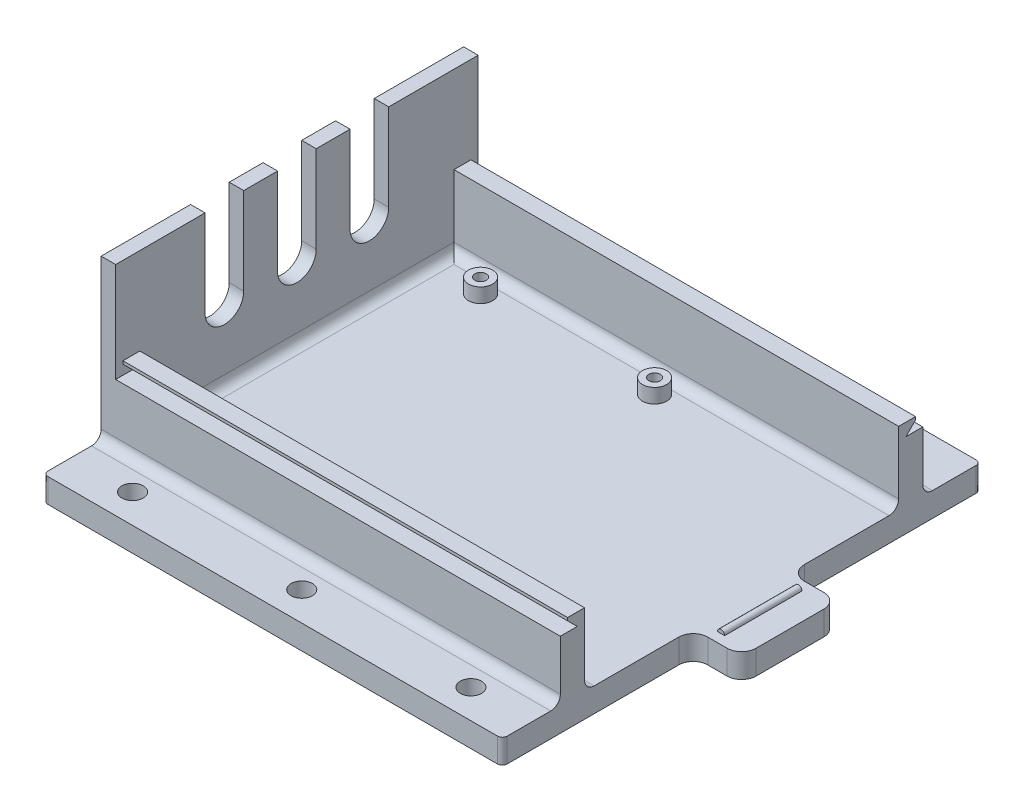
SolidWorks part; units mm, degrees
ref_plane "Front Plane" through (0, 0, 0) normal (0, 0, 1) x (1, 0, 0)
ref_plane "Top Plane" through (0, 0, 0) normal (0, 1, 0) x (1, 0, 0)
ref_plane "Right Plane" through (0, 0, 0) normal (1, 0, 0) x (0, 0, -1)
sketch "Sketch1" plane through (0, 0, 0) normal (0, 1, 0) x (1, 0, 0)
  line L0 (47.5, 13) -> (47.5, 49.5)
  line L1 (-47.5, -49.5) -> (47.5, -49.5)
  line L2 (-47.5, -49.5) -> (-47.5, 49.5)
  line L3 (-47.5, 49.5) -> (47.5, 49.5)
  line L4 (47.5, -49.5) -> (47.5, -13)
  line L5 (-47.5, -49.5) -> (47.5, 49.5) construction
  line L6 (-47.5, 49.5) -> (47.5, -49.5) construction
  line L7 (50.5, 10) -> (54.5, 10)
  line L9 (50.5, -10) -> (54.5, -10)
  line L10 (57.5, 7) -> (57.5, -7)
  arc A0 (54.5, 10) -> (57.5, 7) centre (54.5, 7) cw
  arc A1 (54.5, -10) -> (57.5, -7) centre (54.5, -7) ccw
  arc A2 (47.5, -13) -> (50.5, -10) centre (50.5, -13) cw
  arc A3 (50.5, 10) -> (47.5, 13) centre (50.5, 13) cw
  point P0 (0, 0)
  point P10 (57.5, 0)
  point P13 (57.5, 10)
  point P16 (57.5, -10)
  point P21 (47.5, 10)
  dimension "D5" = 3
  dimension "D1" = 95
  dimension "D2" = 99
  dimension "D3" = 20
  dimension "D4" = 10
extrude "Boss-Extrude1" add sketch "Sketch1" along normal blind 5
sketch "Sketch2" plane through (0, 5, 0) normal (0, 1, 0) x (1, 0, 0)
  line L0 (-47.5, 49.5) -> (-47.5, -49.5) construction
  line L1 (-47.5, 37.5) -> (47.5, 37.5)
  line L3 (-47.5, 32.5) -> (47.5, 32.5)
  line L4 (47.5, 37.5) -> (47.5, 32.5)
  line L5 (47.5, -49.5) -> (47.5, -13) construction
  line L6 (-47.5, -49.5) -> (47.5, -49.5) construction
  line L7 (-47.5, -32.5) -> (47.5, -32.5)
  line L9 (-47.5, -37.5) -> (47.5, -37.5)
  line L10 (47.5, -32.5) -> (47.5, -37.5)
  line L15 (47.5, 49.5) -> (-47.5, 49.5) construction
  line L16 (-47.5, 37.5) -> (-47.5, 32.5)
  line L17 (-47.5, -32.5) -> (-47.5, -37.5)
  dimension "D1" = 5
  dimension "D2" = 5
  dimension "D3" = 12
  dimension "D4" = 12
extrude "Boss-Extrude2" add sketch "Sketch2" along normal blind 15
sketch "Sketch3" plane through (0, 5, 0) normal (0, 1, 0) x (1, 0, 0)
  line L1 (-47.5, 37.5) -> (-44.5, 37.5)
  line L2 (-47.5, 37.5) -> (-47.5, -37.5)
  line L3 (-47.5, -37.5) -> (-44.5, -37.5)
  line L4 (-44.5, 37.5) -> (-44.5, -37.5)
  line L6 (-47.5, 32.5) -> (-47.5, -32.5) construction
  line L7 (47.5, 37.5) -> (-47.5, 37.5) construction
  line L8 (-47.5, -37.5) -> (47.5, -37.5) construction
  point P7 (0, 0)
  point P8 (-46.9834, 35.4125)
  point P14 (0, 0)
  dimension "D1" = 3
extrude "Boss-Extrude3" add sketch "Sketch3" along normal blind 33
sketch "Sketch4" plane through (0, 5, 0) normal (0, 1, 0) x (1, 0, 0)
  line L0 (-34.5, 28) -> (-34.5, -28) construction
  line L1 (-44.5, 0) -> (47.5, 0) construction
  line L2 (-44.5, -32.5) -> (-44.5, 32.5) construction
  circle A0 centre (-34.5, 28) radius 2.5
  circle A1 centre (-34.5, -28) radius 2.5
  circle A2 centre (1.5, 28) radius 2.5
  circle A3 centre (1.5, -28) radius 2.5
  circle A4 centre (-34.5, 28) radius 1.175
  circle A5 centre (1.5, 28) radius 1.175
  circle A6 centre (-34.5, -28) radius 1.175
  circle A7 centre (1.5, -28) radius 1.175
  point P18 (-34.5, 0)
  point P19 (0, 0)
  dimension "D1" = 5
  dimension "D2" = 2.35
  dimension "D3" = 56
  dimension "D4" = 36
  dimension "D5" = 10
extrude "Boss-Extrude4" add sketch "Sketch4" along normal blind 3
sketch "Sketch5" plane through (-44.5, 0, 0) normal (1, 0, 0) x (0, 0, -1)
  line L0 (-32.5, 5) -> (32.5, 5) construction
  line L1 (-19, 20) -> (-19, 38)
  line L2 (-37.5, 38) -> (37.5, 38) construction
  line L3 (-19, 38) -> (-11, 38)
  line L4 (-11, 38) -> (-11, 20)
  line L5 (-4, 20) -> (-4, 38)
  line L6 (-4, 38) -> (4, 38)
  line L7 (4, 38) -> (4, 20)
  line L8 (11, 20) -> (11, 38)
  line L9 (11, 38) -> (19, 38)
  line L10 (19, 38) -> (19, 20)
  arc A0 (-19, 20) -> (-11, 20) centre (-15, 20) ccw
  arc A1 (11, 20) -> (19, 20) centre (15, 20) ccw
  arc A2 (-4, 20) -> (4, 20) centre (0, 20) ccw
  point P10 (0, 5)
  dimension "D3" = 8
  dimension "D4" = 15
  dimension "D1" = 15
  dimension "D2" = 15
extrude "Cut-Extrude1" cut sketch "Sketch5" against normal through all
sketch "Sketch6" plane through (0, 5, 0) normal (0, 1, 0) x (1, 0, 0)
  line L0 (47.5, 49.5) -> (-47.5, 49.5) construction
  line L1 (57.2793, 0) -> (-64.2588, 0) construction
  circle A0 centre (-35, 43.5) radius 2.2
  circle A1 centre (0, 43.5) radius 2.2
  circle A2 centre (35, 43.5) radius 2.2
  circle A3 centre (35, -43.5) radius 2.2
  circle A4 centre (0, -43.5) radius 2.2
  circle A5 centre (-35, -43.5) radius 2.2
  dimension "D1" = 4.4
  dimension "D2" = 6
  dimension "D3" = 35
  dimension "D4" = 35
extrude "Cut-Extrude2" cut sketch "Sketch6" against normal through all
sketch "Sketch7" plane through (47.5, 0, 0) normal (1, 0, 0) x (0, 0, -1)
  line L0 (0, 25.7856) -> (0, -7.9871) construction
  line L4 (-36, 19.4) -> (-34, 17.4)
  line L5 (-34, 17.4) -> (-37.5, 17.4)
  line L9 (-37.5, 20) -> (-37.5, 5) construction
  line L11 (32.5, 20) -> (37.5, 20) construction
  line L12 (-36, 19.4) -> (-36, 20)
  line L13 (-36, 20) -> (-37.5, 20)
  line L14 (-37.5, 20) -> (-37.5, 17.4)
  line L16 (37.5, 20) -> (37.5, 17.4)
  line L17 (36, 20) -> (37.5, 20)
  line L18 (36, 19.4) -> (36, 20)
  line L19 (34, 17.4) -> (37.5, 17.4)
  line L20 (36, 19.4) -> (34, 17.4)
  dimension "D1" = 1.5
  dimension "D2" = 2.6
  dimension "D3" = 45
  dimension "D4" = 0.6
extrude "Cut-Extrude3" cut sketch "Sketch7" against normal up to surface (92 mm away) up to face at (-44.5, 25.1, 0)
fillet "Fillet1" radius 1 4 edges at (-47.5, 2.5, -49.5) (-47.5, 2.5, 49.5) (47.5, 2.5, 49.5) (47.5, 2.5, -49.5)
fillet "Fillet2" radius 2 5 edges at (0, 5, -37.5) (1.5, 5, -32.5) (-44.5, 5, 0) (1.5, 5, 32.5) (0, 5, 37.5)
sketch "Sketch9" plane through (0, 0, 10) normal (0, 0, 1) x (1, 0, 0)
  line L0 (50.5, 5) -> (52, 5)
  line L1 (47.5, 5) -> (47.5, 0) construction
  line L2 (50.5, 5) -> (54.5, 5) construction
  arc A0 (50.5, 5) -> (52, 5) centre (51.25, 5) cw
  point P4 (0, 0)
  dimension "D1" = 1.5
  dimension "D2" = 3
extrude "Boss-Extrude5" add sketch "Sketch9" against normal blind 16 from offset 2 offset against normal yes
